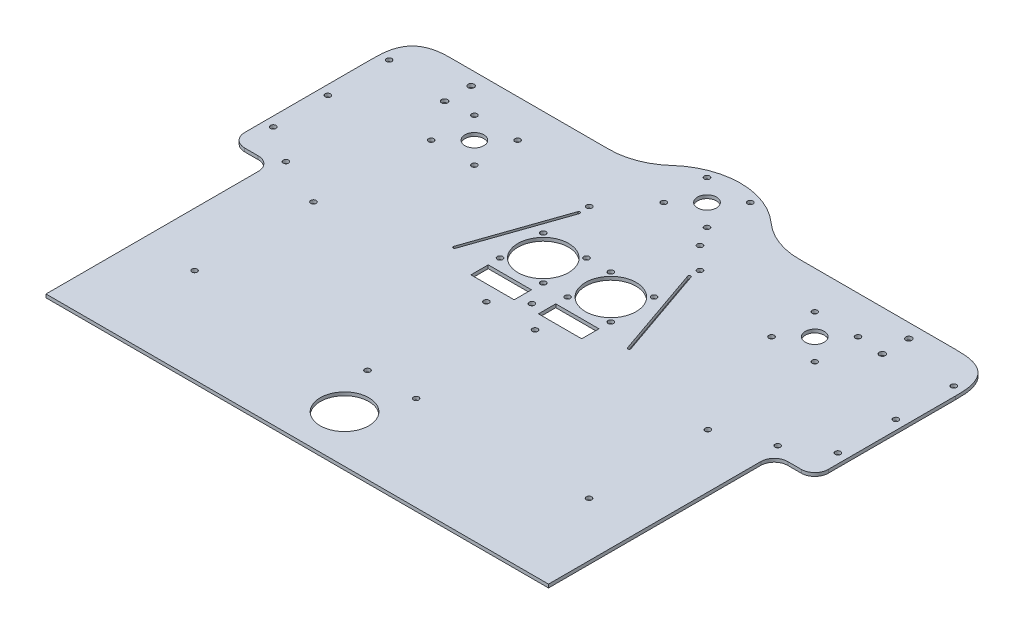
SolidWorks part; units mm, degrees
ref_plane "Front Plane" through (0, 0, 0) normal (0, 0, 1) x (1, 0, 0)
ref_plane "Top Plane" through (0, 0, 0) normal (0, 1, 0) x (1, 0, 0)
ref_plane "Right Plane" through (0, 0, 0) normal (1, 0, 0) x (0, 0, -1)
sketch "Sketch1" plane through (0, 0, 0) normal (0, 1, 0) x (1, 0, 0)
  line L1 (-103.134, 171.9149) -> (328.866, 171.9149)
  line L2 (-103.134, 171.9149) -> (-103.134, -28.0851)
  line L3 (-103.134, -28.0851) -> (328.866, -28.0851)
  line L4 (328.866, 171.9149) -> (328.866, -28.0851)
extrude "Boss-Extrude1" add sketch "Sketch1" along normal blind 2.5 contours L1 L4 L3 L2
sketch "Sketch3" plane through (0, 2.5, 0) normal (0, 1, 0) x (1, 0, 0)
  line L0 (-13.134, 71.9149) -> (-29.1359, 55.9131)
  line L1 (2.8678, 87.9167) -> (-29.1359, 87.9167)
  line L2 (2.8678, 87.9167) -> (2.8678, 55.9131)
  line L3 (2.8678, 55.9131) -> (-29.1359, 55.9131)
  line L4 (-29.1359, 87.9167) -> (-29.1359, 55.9131)
  line L5 (2.8678, 87.9167) -> (-29.1359, 55.9131) construction
  line L6 (2.8678, 55.9131) -> (-29.1359, 87.9167) construction
  line L7 (-103.134, 71.9149) -> (-13.134, 71.9149)
  line L8 (-103.134, 171.9149) -> (-103.134, -28.0851) construction
  line L9 (238.866, 71.9149) -> (238.866, 115.9149)
  line L14 (62.253, -0.3819) -> (46.2512, -16.3837)
  line L15 (238.866, 115.9149) -> (328.866, 115.9149)
  line L18 (328.866, 171.9149) -> (328.866, -28.0851) construction
  line L19 (238.866, 71.9149) -> (222.8641, 55.9131)
  line L20 (254.8678, 87.9167) -> (222.8641, 87.9167)
  line L21 (254.8678, 87.9167) -> (254.8678, 55.9131)
  line L22 (254.8678, 55.9131) -> (222.8641, 55.9131)
  line L23 (222.8641, 87.9167) -> (222.8641, 55.9131)
  line L24 (254.8678, 87.9167) -> (222.8641, 55.9131) construction
  line L25 (254.8678, 55.9131) -> (222.8641, 87.9167) construction
  line L27 (328.866, 71.9149) -> (238.866, 71.9149)
  line L28 (238.866, 115.9149) -> (238.866, 171.9149)
  line L29 (238.866, 171.9149) -> (328.866, 171.9149)
  line L30 (328.866, 115.9149) -> (328.866, 171.9149)
  line L31 (328.866, 115.9149) -> (-169.3435, 115.9149)
  line L32 (328.866, 115.9149) -> (328.866, 173.2785)
  line L33 (328.866, 173.2785) -> (-169.3435, 173.2785)
  line L34 (-169.3435, 115.9149) -> (-169.3435, 173.2785)
  line L35 (78.2549, 15.6199) -> (46.2512, 15.6199)
  line L36 (78.2549, 15.6199) -> (78.2549, -16.3837)
  line L37 (78.2549, -16.3837) -> (46.2512, -16.3837)
  line L38 (46.2512, 15.6199) -> (46.2512, -16.3837)
  line L39 (78.2549, 15.6199) -> (46.2512, -16.3837) construction
  line L40 (78.2549, -16.3837) -> (46.2512, 15.6199) construction
  circle A0 centre (-13.134, 71.9149) radius 7
  circle A1 centre (-29.1359, 55.9131) radius 2
  circle A2 centre (-29.1359, 87.9167) radius 2
  circle A3 centre (2.8678, 87.9167) radius 2
  circle A4 centre (2.8678, 55.9131) radius 2
  circle A10 centre (238.866, 71.9149) radius 7
  circle A11 centre (222.8641, 55.9131) radius 2
  circle A12 centre (222.8641, 87.9167) radius 2
  circle A13 centre (254.8678, 87.9167) radius 2
  circle A14 centre (254.8678, 55.9131) radius 2
  circle A15 centre (62.253, -0.3819) radius 7
  circle A16 centre (46.2512, -16.3837) radius 2
  circle A17 centre (46.2512, 15.6199) radius 2
  circle A18 centre (78.2549, 15.6199) radius 2
  circle A19 centre (78.2549, -16.3837) radius 2
  point P10 (328.866, 71.9149)
extrude "Cut-Extrude1" cut sketch "Sketch3" against normal blind 2.5 contours A2 | A3 | A4 | A1 | A0 | A11 | A14 | A13 | A10 | A12 | L32 L31 L34 L33
sketch "Sketch5" plane through (0, 2.5, 0) normal (0, 1, 0) x (1, 0, 0)
  line L0 (263.7413, -28.0851) -> (263.7413, -18.0851)
  line L3 (-103.134, -28.0851) -> (328.866, -28.0851) construction
  line L5 (263.7413, -18.0851) -> (328.866, -18.0851)
  line L6 (263.7413, -18.0851) -> (263.7413, -28.0851)
  line L7 (263.7413, -28.0851) -> (328.866, -28.0851)
  line L8 (328.866, -18.0851) -> (328.866, -28.0851)
  line L9 (263.7413, -18.0851) -> (-103.134, -18.0851)
  line L10 (263.7413, -18.0851) -> (263.7413, -28.0851)
  line L11 (263.7413, -28.0851) -> (-103.134, -28.0851)
  line L12 (-103.134, -18.0851) -> (-103.134, -28.0851)
  line M12 (328.866, -28.0851) -> (328.866, 115.9149)
  line M14 (-103.134, 115.9149) -> (-103.134, -28.0851)
  line M15 (-103.134, -28.0851) -> (328.866, -28.0851)
extrude "Cut-Extrude3" cut sketch "Sketch5" against normal blind 2.5 contours L0 L9 M14 M15 | L5 L0 M15 M12 region at (80.3036, 2.5, 23.0851) region at (296.3036, 2.5, 23.0851)
sketch "Sketch6" plane through (0, 2.5, 0) normal (0, 1, 0) x (1, 0, 0)
  line L0 (328.866, -18.0851) -> (-103.134, -18.0851) construction
  line L1 (112.866, -18.0851) -> (112.866, 21.9149)
  line L2 (112.866, 21.9149) -> (137.866, 21.9149)
  line L3 (112.866, 21.9149) -> (87.866, 21.9149)
  line L4 (87.866, 21.9149) -> (71.8641, 5.9131)
  line L5 (103.8678, 37.9167) -> (71.8641, 37.9167)
  line L6 (103.8678, 37.9167) -> (103.8678, 5.9131)
  line L7 (103.8678, 5.9131) -> (71.8641, 5.9131)
  line L8 (71.8641, 37.9167) -> (71.8641, 5.9131)
  line L9 (103.8678, 37.9167) -> (71.8641, 5.9131) construction
  line L10 (103.8678, 5.9131) -> (71.8641, 37.9167) construction
  line L11 (137.866, 21.9149) -> (121.8641, 5.9131)
  line L12 (153.8678, 37.9167) -> (121.8641, 37.9167)
  line L13 (153.8678, 37.9167) -> (153.8678, 5.9131)
  line L14 (153.8678, 5.9131) -> (121.8641, 5.9131)
  line L15 (121.8641, 37.9167) -> (121.8641, 5.9131)
  line L16 (153.8678, 37.9167) -> (121.8641, 5.9131) construction
  line L17 (153.8678, 5.9131) -> (121.8641, 37.9167) construction
  circle A0 centre (137.866, 21.9149) radius 18.75
  circle A1 centre (87.866, 21.9149) radius 18.75
  circle A2 centre (87.866, 21.9149) radius 7
  circle A3 centre (71.8641, 5.9131) radius 2
  circle A4 centre (71.8641, 37.9167) radius 2
  circle A5 centre (103.8678, 37.9167) radius 2
  circle A6 centre (103.8678, 5.9131) radius 2
  circle A7 centre (137.866, 21.9149) radius 7
  circle A8 centre (121.8641, 5.9131) radius 2
  circle A9 centre (121.8641, 37.9167) radius 2
  circle A10 centre (153.8678, 37.9167) radius 2
  circle A11 centre (153.8678, 5.9131) radius 2
  point P0 (112.866, -18.0851)
extrude "Cut-Extrude4" cut sketch "Sketch6" against normal blind 2.5 contours A11 | A8 | A10 | A9 | A5 | A6 | A3 | A4
sketch "Sketch8" plane through (0, 2.5, 0) normal (0, 1, 0) x (1, 0, 0)
  line L2 (153.8678, 5.9131) -> (153.8678, 90.0973)
  line L3 (153.8678, 90.0973) -> (71.8641, 90.0973)
  line L4 (71.8641, 90.0973) -> (71.8641, 5.9131)
  line L5 (153.8678, 64.0929) -> (71.8641, 64.0929)
  line L10 (177.527, -4.0851) -> (153.8678, 64.0929) construction
  line L14 (176.5823, -4.4129) -> (152.9231, 63.7651)
  line L15 (178.4718, -3.7572) -> (154.8125, 64.4208)
  line L16 (48.2049, -4.0851) -> (71.8641, 64.0929) construction
  line L17 (47.2602, -3.7572) -> (70.9194, 64.4208)
  line L18 (49.1496, -4.4129) -> (72.8089, 63.7651)
  arc A6 (176.5823, -4.4129) -> (178.4718, -3.7572) centre (177.527, -4.0851) ccw
  arc A7 (154.8125, 64.4208) -> (152.9231, 63.7651) centre (153.8678, 64.0929) ccw
  arc A8 (47.2602, -3.7572) -> (49.1496, -4.4129) centre (48.2049, -4.0851) ccw
  arc A9 (72.8089, 63.7651) -> (70.9194, 64.4208) centre (71.8641, 64.0929) ccw
  point P17 (177.527, 5.9131)
  point P18 (48.2049, 5.9131)
  point P19 (165.6974, 30.0039)
  point P22 (112.866, -4.0851)
  point P27 (60.0345, 30.0039)
extrude "Cut-Extrude5" cut sketch "Sketch8" against normal blind 2.5 contours L17 A9 L18 A8 | L15 A7 L14 A6
fillet "Fillet1" radius 30 2 edges at (-103.134, 1.25, -115.9149) (328.866, 1.25, -115.9149) curvature continuous yes
sketch "Sketch9" plane through (0, 2.5, 0) normal (0, 1, 0) x (1, 0, 0)
  line L0 (328.866, 62.6221) -> (321.866, 62.6221)
  line L1 (328.866, 85.9149) -> (328.866, -18.0851) construction
  line L2 (321.866, 109.7214) -> (321.866, -11.8915)
  line L3 (321.866, 6.0103) -> (321.866, -11.8915)
  line L4 (321.866, 109.7214) -> (321.866, 91.8196)
  line L5 (321.866, 91.8196) -> (321.866, 109.7214)
  line L6 (-103.134, 46.4673) -> (-96.134, 46.4673)
  line L7 (-103.134, 85.9149) -> (-103.134, -18.0851) construction
  line L8 (-96.134, 46.4673) -> (-96.134, 109.7214)
  line L9 (-96.134, 109.7214) -> (-96.134, -11.8916)
  line L10 (-96.134, -11.8916) -> (-96.134, 6.0103)
  line L11 (-96.134, 109.7214) -> (-96.134, 97.3154)
  line L12 (-96.134, 109.7214) -> (-96.134, 91.8196)
  circle A0 centre (321.866, 6.0103) radius 2
  circle A1 centre (321.866, 48.9149) radius 2
  circle A2 centre (321.866, 91.8196) radius 2
  circle A3 centre (-96.134, 46.4673) radius 2
  circle A4 centre (-96.134, 91.8196) radius 2
  circle A5 centre (-96.134, 6.0103) radius 2
  spline S0 degree 2 poles (328.866, 85.9149) (328.866, 87.9765) (328.8467, 89.0459) (328.8162, 90.7467) (328.7231, 92.1742) (328.5043, 95.5283) (327.8783, 98.3317) (326.3274, 105.2776) (322.2688, 109.3319) (318.2198, 113.3765) (311.2895, 114.9258) (308.4764, 115.5546) (305.1048, 115.7733) (303.6844, 115.8655) (301.9893, 115.8958) (300.9233, 115.9149) (298.866, 115.9149) knots 0 0 0 0.0625 0.0625 0.125 0.125 0.25 0.25 0.5 0.5 0.75 0.75 0.875 0.875 0.9375 0.9375 1 1 1 construction
  spline S1 degree 2 poles (298.866, -18.0851) (300.9275, -18.0851) (301.997, -18.0659) (303.6978, -18.0353) (305.1253, -17.9422) (308.4794, -17.7234) (311.2827, -17.0975) (318.2287, -15.5466) (322.283, -11.4879) (326.3276, -7.4389) (327.8768, -0.5086) (328.5057, 2.3045) (328.7244, 5.6761) (328.8165, 7.0965) (328.8469, 8.7916) (328.866, 9.8575) (328.866, 11.9149) knots 0 0 0 0.0625 0.0625 0.125 0.125 0.25 0.25 0.5 0.5 0.75 0.75 0.875 0.875 0.9375 0.9375 1 1 1 construction
  spline S2 degree 2 poles (-73.134, 115.9149) (-75.1956, 115.9149) (-76.2651, 115.8957) (-77.9658, 115.8651) (-79.3933, 115.772) (-82.7474, 115.5532) (-85.5508, 114.9273) (-92.4967, 113.3764) (-96.551, 109.3177) (-100.5957, 105.2687) (-102.1449, 98.3384) (-102.7737, 95.5254) (-102.9924, 92.1538) (-103.0846, 90.7333) (-103.1149, 89.0383) (-103.134, 87.9723) (-103.134, 85.9149) knots 0 0 0 0.0625 0.0625 0.125 0.125 0.25 0.25 0.5 0.5 0.75 0.75 0.875 0.875 0.9375 0.9375 1 1 1 construction
  spline S3 degree 2 poles (-103.134, 11.9149) (-103.134, 9.8534) (-103.1148, 8.7839) (-103.0842, 7.0831) (-102.9911, 5.6556) (-102.7723, 2.3015) (-102.1464, -0.5019) (-100.5955, -7.4478) (-96.5368, -11.5021) (-92.4879, -15.5467) (-85.5575, -17.0959) (-82.7445, -17.7248) (-79.3729, -17.9435) (-77.9525, -18.0356) (-76.2574, -18.066) (-75.1914, -18.0851) (-73.134, -18.0851) knots 0 0 0 0.0625 0.0625 0.125 0.125 0.25 0.25 0.5 0.5 0.75 0.75 0.875 0.875 0.9375 0.9375 1 1 1 construction
extrude "Cut-Extrude6" cut sketch "Sketch9" against normal blind 2.5 contours A0 | A1 | A2 | A5 | A3 | A4
sketch "Sketch10" plane through (0, 2.5, 0) normal (0, 1, 0) x (1, 0, 0)
  line L0 (232.1904, -18.0851) -> (232.1904, -11.5851)
  line L1 (328.866, -18.0851) -> (-103.134, -18.0851) construction
  line L2 (322.1851, -11.5851) -> (-96.4532, -11.5851)
  line L3 (322.1851, -11.5851) -> (232.1904, -11.5851)
  line L4 (322.1851, -11.5851) -> (232.1904, -11.5851)
  line L5 (322.1851, -11.5851) -> (232.1904, -11.5851)
  line L6 (322.1851, -11.5851) -> (294.9418, -11.5851)
  line L7 (-96.4532, -11.5851) -> (-78.7572, -11.5851)
  line L8 (-96.4532, -11.5851) -> (-69.2097, -11.5851)
  circle A0 centre (112.866, -11.5851) radius 2
  circle A3 centre (294.9418, -11.5851) radius 2
  circle A4 centre (-69.2097, -11.5851) radius 2
  spline S0 degree 2 poles (298.866, -18.0851) (300.9275, -18.0851) (301.997, -18.0659) (303.6978, -18.0353) (305.1253, -17.9422) (308.4794, -17.7234) (311.2827, -17.0975) (318.2287, -15.5466) (322.283, -11.4879) (326.3276, -7.4389) (327.8768, -0.5086) (328.5057, 2.3045) (328.7244, 5.6761) (328.8165, 7.0965) (328.8469, 8.7916) (328.866, 9.8575) (328.866, 11.9149) knots 0 0 0 0.0625 0.0625 0.125 0.125 0.25 0.25 0.5 0.5 0.75 0.75 0.875 0.875 0.9375 0.9375 1 1 1 construction
  spline S1 degree 2 poles (-103.134, 11.9149) (-103.134, 9.8534) (-103.1148, 8.7839) (-103.0842, 7.0831) (-102.9911, 5.6556) (-102.7723, 2.3015) (-102.1464, -0.5019) (-100.5955, -7.4478) (-96.5368, -11.5021) (-92.4879, -15.5467) (-85.5575, -17.0959) (-82.7445, -17.7248) (-79.3729, -17.9435) (-77.9525, -18.0356) (-76.2574, -18.066) (-75.1914, -18.0851) (-73.134, -18.0851) knots 0 0 0 0.0625 0.0625 0.125 0.125 0.25 0.25 0.5 0.5 0.75 0.75 0.875 0.875 0.9375 0.9375 1 1 1 construction
extrude "Cut-Extrude7" cut sketch "Sketch10" against normal blind 2.5 contours A4 | A0 | A3
extrude "Cut-Extrude8" cut sketch "Sketch6<3>" against normal blind 10 contours A1 | A0
sketch "Sketch6<3>" plane through (0, 2.5, 0) normal (0, 1, 0) x (1, 0, 0) same geometry as "Sketch6"
sketch "Sketch12" plane through (0, 2.5, 0) normal (0, 1, 0) x (1, 0, 0)
  line L0 (121.8641, 37.9167) -> (121.8641, 71.9149)
  line L1 (238.866, 71.9149) -> (-13.134, 71.9149)
  line L3 (121.8641, 71.9149) -> (105.8623, 55.9131)
  line L4 (137.866, 87.9167) -> (105.8623, 87.9167)
  line L5 (137.866, 87.9167) -> (137.866, 55.9131)
  line L6 (137.866, 55.9131) -> (105.8623, 55.9131)
  line L7 (105.8623, 87.9167) -> (105.8623, 55.9131)
  line L8 (137.866, 87.9167) -> (105.8623, 55.9131) construction
  line L9 (137.866, 55.9131) -> (105.8623, 87.9167) construction
  circle A1 centre (121.8641, 71.9149) radius 7
  circle A2 centre (105.8623, 55.9131) radius 2
  circle A3 centre (105.8623, 87.9167) radius 2
  circle A4 centre (137.866, 87.9167) radius 2
  circle A5 centre (137.866, 55.9131) radius 2
extrude "Cut-Extrude9" cut sketch "Sketch12" against normal blind 10 contours A4
sketch "Sketch13" plane through (0, 2.5, 0) normal (0, 1, 0) x (1, 0, 0)
  line L0 (328.866, 85.9149) -> (274.866, 85.9149)
  line L1 (274.866, 85.9149) -> (274.866, 105.5149)
  line L2 (-103.134, 85.9149) -> (-49.134, 85.9149)
  line L3 (-49.134, 85.9149) -> (-49.134, 105.5149)
  circle A0 centre (274.866, 85.9149) radius 2.25
  circle A1 centre (274.866, 105.5149) radius 2.25
  circle A2 centre (-49.134, 85.9149) radius 2.25
  circle A3 centre (-49.134, 105.5149) radius 2.25
extrude "Cut-Extrude10" cut sketch "Sketch13" against normal blind 10 contours A0 | A1 | A2 | A3
sketch "Sketch14" plane through (0, 2.5, 0) normal (0, 1, 0) x (1, 0, 0)
  line L0 (153.8678, 37.9167) -> (121.8641, 71.9149)
  line L1 (121.8641, 71.9149) -> (153.8678, 71.9149)
  line L2 (71.8641, 37.9167) -> (71.8641, 71.9149)
  circle A0 centre (153.8678, 71.9149) radius 2
  circle A1 centre (71.8641, 71.9149) radius 2
extrude "Cut-Extrude12" cut sketch "Sketch14" against normal blind 2.5 contours A0 | A1
sketch "Sketch19" plane through (0, 2.5, 0) normal (0, 1, 0) x (1, 0, 0)
  line L0 (-73.134, -18.0851) -> (298.866, -18.0851)
  line L1 (-73.134, -18.0851) -> (-73.134, -185.2034)
  line L2 (298.866, -18.0851) -> (298.866, -185.2034)
  line L3 (-73.134, -185.2034) -> (298.866, -185.2034)
extrude "Boss-Extrude5" add sketch "Sketch19" against normal blind 2.5
fillet "Fillet3" radius 10 4 edges at (-103.134, 1.25, 18.0851) (-73.134, 1.25, 18.0851) (328.866, 1.25, 18.0851) (298.866, 1.25, 18.0851)
sketch "Sketch21" plane through (0, 2.5, 0) normal (0, 1, 0) x (1, 0, 0)
  line L1 (298.866, -185.2034) -> (258.866, -185.2034)
  line L2 (298.866, -185.2034) -> (298.866, -115.2034)
  line L3 (298.866, -115.2034) -> (258.866, -115.2034)
  line L4 (258.866, -185.2034) -> (258.866, -115.2034)
  line L5 (258.866, -115.2034) -> (130.866, -115.2034)
  line L6 (258.866, -115.2034) -> (258.866, -27.2034)
  line L7 (258.866, -27.2034) -> (130.866, -27.2034)
  line L8 (130.866, -115.2034) -> (130.866, -27.2034)
  line L9 (-73.134, -185.2034) -> (-33.134, -185.2034)
  line L10 (-73.134, -185.2034) -> (-73.134, -115.2034)
  line L11 (-73.134, -115.2034) -> (-33.134, -115.2034)
  line L12 (-33.134, -185.2034) -> (-33.134, -115.2034)
  line L13 (-33.134, -115.2034) -> (94.866, -115.2034)
  line L14 (-33.134, -115.2034) -> (-33.134, -27.2034)
  line L15 (-33.134, -27.2034) -> (94.866, -27.2034)
  line L16 (94.866, -115.2034) -> (94.866, -27.2034)
  circle A0 centre (258.866, -115.2034) radius 2
  circle A1 centre (130.866, -115.2034) radius 2
  circle A2 centre (94.866, -115.2034) radius 2
  circle A3 centre (-33.134, -115.2034) radius 2
  circle A4 centre (-33.134, -27.2034) radius 2
  circle A5 centre (94.866, -27.2034) radius 2
  circle A6 centre (258.866, -27.2034) radius 2
  circle A7 centre (130.866, -27.2034) radius 2
extrude "Cut-Extrude14" cut sketch "Sketch21" against normal blind 2.5 contours A0 | A6 | A7 | A5 | A1 | A2 | A4 | A3
sketch "Sketch22" plane through (0, 2.5, 0) normal (0, 1, 0) x (1, 0, 0)
  line L0 (121.8641, 5.9131) -> (121.8641, -11.5851)
  line L1 (153.8678, 5.9131) -> (153.8678, -11.5851)
  line L2 (103.8678, 5.9131) -> (103.8678, -20.5636)
  line L3 (153.8678, -2.836) -> (121.8641, -2.836)
  line L4 (153.8678, -2.836) -> (153.8678, -20.5636)
  line L5 (153.8678, -20.5636) -> (121.8641, -20.5636)
  line L6 (121.8641, -2.836) -> (121.8641, -20.5636)
  line L7 (71.8641, 5.9131) -> (71.8641, -20.5636)
  line L8 (121.8641, -20.5636) -> (121.8641, -15.0679)
  line L9 (103.8678, -20.5636) -> (71.8641, -20.5636)
  line L10 (103.8678, -20.5636) -> (103.8678, -2.836)
  line L11 (103.8678, -2.836) -> (71.8641, -2.836)
  line L12 (71.8641, -20.5636) -> (71.8641, -2.836)
  line L13 (121.8641, -20.5636) -> (121.8641, -18.0057)
  line L14 (153.8678, -20.5636) -> (153.8678, -16.8822)
  line L15 (153.8678, -20.5636) -> (153.8678, -15.6536)
  line L16 (153.8678, -15.6536) -> (121.8641, -15.6536)
  line L17 (121.8641, -15.6536) -> (103.8678, -15.6536)
  line L18 (103.8678, -15.6536) -> (71.8641, -15.6536)
extrude "Cut-Extrude15" cut sketch "Sketch22" against normal blind 10 contours L0 L6 L5 L4 L1 L3 | L2 L11 L7 L9 region at (137.866, 2.5, 9.2448) region at (87.866, 2.5, 9.2448)
sketch "Sketch23" plane through (0, 2.5, 0) normal (0, 1, 0) x (1, 0, 0)
  line L1 (-73.134, -185.2034) -> (-38.134, -185.2034)
  line L2 (-73.134, -185.2034) -> (-73.134, -150.2034)
  line L3 (-73.134, -150.2034) -> (-38.134, -150.2034)
  line L4 (-38.134, -185.2034) -> (-38.134, -150.2034)
  circle A0 centre (-38.134, -150.2034) radius 18
sketch "Sketch24" plane through (0, 2.5, 0) normal (0, 1, 0) x (1, 0, 0)
  line L1 (298.866, -185.2034) -> (263.866, -185.2034)
  line L2 (298.866, -185.2034) -> (298.866, -150.2034)
  line L3 (298.866, -150.2034) -> (263.866, -150.2034)
  line L4 (263.866, -185.2034) -> (263.866, -150.2034)
  circle A0 centre (263.866, -150.2034) radius 18
sketch "Sketch26" plane through (0, 2.5, 0) normal (0, 1, 0) x (1, 0, 0)
  line L0 (112.866, -11.5851) -> (112.866, 115.9149)
  line L1 (298.866, 115.9149) -> (-73.134, 115.9149) construction
  line L2 (112.866, 115.9149) -> (112.866, 119.8149)
  line L3 (160.2063, 115.9149) -> (65.5257, 115.9149)
  arc A0 (65.5257, 115.9149) -> (160.2063, 115.9149) centre (112.866, 87.9167) cw
extrude "Boss-Extrude6" add sketch "Sketch26" against normal blind 2.5 contours A0 L3
sketch "Sketch27" plane through (0, 2.5, 0) normal (0, 1, 0) x (1, 0, 0)
  line L0 (160.2063, 115.9149) -> (65.5257, 115.9149)
  line L1 (112.866, 115.9149) -> (112.866, 118.1149)
  line L2 (112.866, 118.1149) -> (112.866, 118.1169)
  line L3 (298.6293, -177.6896) -> (282.6274, -193.6915)
  line L4 (314.6311, -161.6878) -> (282.6274, -161.6878)
  line L5 (314.6311, -161.6878) -> (314.6311, -193.6915)
  line L6 (314.6311, -193.6915) -> (282.6274, -193.6915)
  line L7 (282.6274, -161.6878) -> (282.6274, -193.6915)
  line L8 (314.6311, -161.6878) -> (282.6274, -193.6915) construction
  line L9 (314.6311, -193.6915) -> (282.6274, -161.6878) construction
  line L10 (112.866, 118.1169) -> (96.8641, 102.115)
  line L11 (128.8678, 134.1187) -> (96.8641, 134.1187)
  line L12 (128.8678, 134.1187) -> (128.8678, 102.115)
  line L13 (128.8678, 102.115) -> (96.8641, 102.115)
  line L14 (96.8641, 134.1187) -> (96.8641, 102.115)
  line L15 (128.8678, 134.1187) -> (96.8641, 102.115) construction
  line L16 (128.8678, 102.115) -> (96.8641, 134.1187) construction
  arc A0 (160.2063, 115.9149) -> (65.5257, 115.9149) centre (112.866, 87.9167) ccw construction
  circle A1 centre (298.6293, -177.6896) radius 18.75
  circle A2 centre (298.6293, -177.6896) radius 7
  circle A3 centre (282.6274, -193.6915) radius 2
  circle A4 centre (282.6274, -161.6878) radius 2
  circle A5 centre (314.6311, -161.6878) radius 2
  circle A6 centre (314.6311, -193.6915) radius 2
  circle A7 centre (112.866, 118.1169) radius 18.75
  circle A8 centre (112.866, 118.1169) radius 7
  circle A9 centre (96.8641, 102.115) radius 2
  circle A10 centre (96.8641, 134.1187) radius 2
  circle A11 centre (128.8678, 134.1187) radius 2
  circle A12 centre (128.8678, 102.115) radius 2
  point P21 (112.866, 118.1169)
extrude "Cut-Extrude18" cut sketch "Sketch27" against normal blind 2.5 contours A11 | A12 | A8 | A9 | A10
sketch "Sketch28" plane through (0, 2.5, 0) normal (0, 1, 0) x (1, 0, 0)
  line L0 (263.866, -150.2034) -> (-38.134, -150.2034)
  circle A1 centre (112.866, -150.2034) radius 18
extrude "Cut-Extrude19" cut sketch "Sketch28" against normal blind 10 contours A1
fillet "Fillet4" radius 50 2 edges at (65.5257, 1.25, -115.9149) (160.2063, 1.25, -115.9149)
